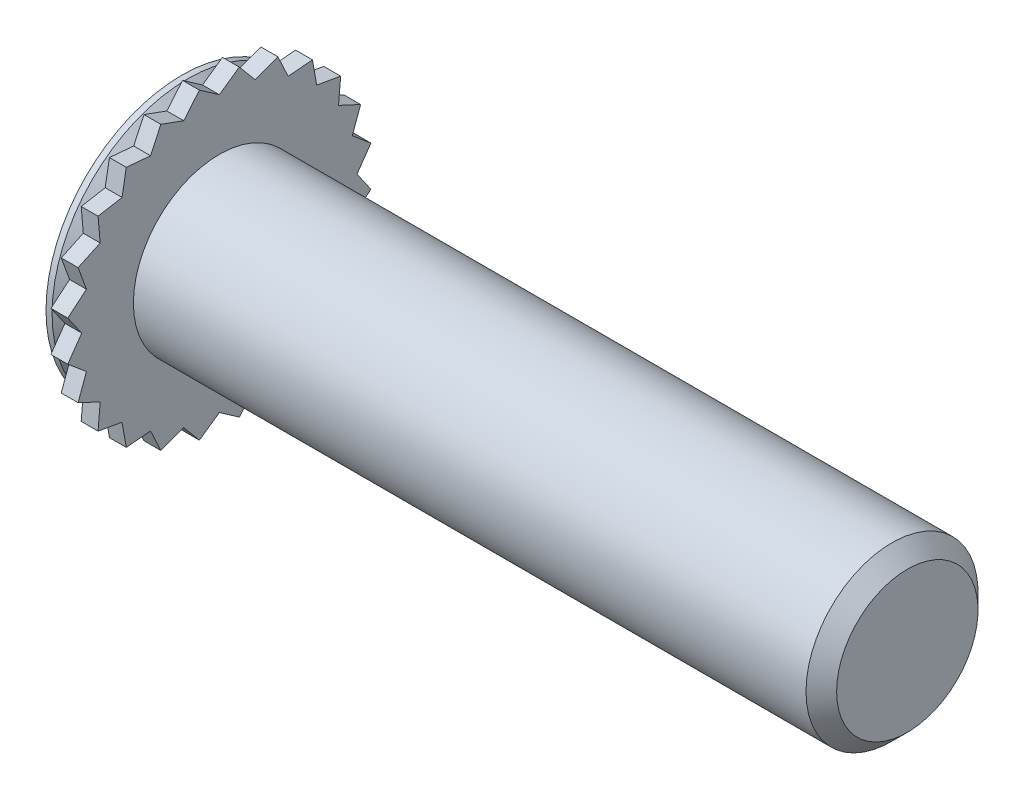
SolidWorks part; units mm, degrees
revolve "BaseBody" add sketch "BodySke" angle 360 about L6 other way angle 15
sketch "BodySke" plane through (0, 0, 0) normal (0, 0, 1) x (1, 0, 0)
  line L0 (0, 2.2225) -> (0, 3.95)
  line L1 (1.09, 4.445) -> (0.5995, 4.445)
  line L2 (0.5995, 4.445) -> (0.5995, 3.6373)
  line L3 (1.09, 2.5) -> (20.645, 2.5)
  line L4 (21.09, 2.055) -> (21.09, 0)
  line L5 (21.09, 0) -> (0.545, 0)
  line L6 (0, 0) -> (50.554, 0) construction
  line L7 (1.09, 4.445) -> (1.09, 2.5)
  line L8 (21.09, 2.055) -> (20.645, 2.5)
  line L9 (0.5995, 3.6373) -> (0.4905, 3.6373)
  line L10 (0.4905, 3.6373) -> (0.1778, 3.95)
  line L11 (1.89, 19.05) -> (1.89, -3.175) construction
  line L12 (0.1778, 3.95) -> (0, 3.95)
  line L13 (0, 2.2225) -> (0.545, 1.6775)
  line L14 (0.545, 1.6775) -> (0.545, 0)
  dimension "Advance" = 0.8
  dimension "Minor_dia" = 4.11
  dimension "Diameter" = 5
  dimension "Length" = 20
  dimension "D1" = 45
cosmetic thread "ThreadCosmetic" [suppressed] parameters "Thread_length"=18.4, "Thread_minor"=4.11
ref_plane "Plane1" through (0, 0, 0) normal (0, 0, 1) x (1, 0, 0)
ref_plane "Plane2" through (0, 0, 0) normal (0, 1, 0) x (1, 0, 0)
ref_plane "Plane3" through (0, 0, 0) normal (1, 0, 0) x (0, 0, -1)
sketch "ThdSchSke" plane through (0, 0, 0) normal (0, 0, 1) x (1, 0, 0)
  line L0 (2.69, -2.055) -> (2.3784, -2.5)
  line L1 (2.69, -2.055) -> (3.0016, -2.5)
  line L2 (3.0016, -2.5) -> (3.0016, -3.125)
  line L3 (-3.175, 0) -> (5.1513, 0) construction
  line L5 (3.0016, -3.125) -> (2.3784, -3.125)
  line L6 (2.3784, -3.125) -> (2.3784, -2.5)
  line L8 (1.09, -2.5) -> (1.09, 2.5) construction
  dimension "Diameter" = 5
  dimension "Thread_minor" = 4.11
  dimension "Start" = 1.6
revolve "ThreadSchematic" [suppressed] cut sketch "ThdSchSke" angle 360 about L3
pattern_linear "ThdSchPat" [suppressed]
sketch "CliRinCutSke" plane through (1.09, 0, 0) normal (1, 0, 0) x (0, 0, -1)
  line L0 (0, 0) -> (0, 4.8256) construction
  line L1 (0.5802, 4.407) -> (0, 4.0005)
  line L2 (0, 4.0005) -> (-0.5802, 4.407)
  arc A0 (0.5802, 4.407) -> (-0.5802, 4.407) centre (0, 0) ccw
  circle A1 centre (0, 0) radius 4.445 construction
  circle A2 centre (0, 0) radius 4.0005 construction
extrude "ClinchCut" cut sketch "CliRinCutSke" against normal blind 0.4905
pattern_circular "ClinchCutPat" count 24 every 15 about axis through (0, 0, 0) along (1, 0, 0) of "ClinchCut"
equation "' \"Length@BodySke\" = 20"
equation "' \"A_dim@BodySke\" = 1.09"
equation "' \"E_dia@BodySke\" = 8.89"
equation "' \"C_dia@BodySke\" = 7.9"
equation "' \"Diameter@BodySke\" = 5"
equation "' \"Minor_dia@BodySke\" = 4.11"
equation "' \"Advance@BodySke\" = 0.8"
equation "\"Face_clr_dia@BodySke\" = \"E_dia@BodySke\" / 2"
equation "\"Face_clr_dep@BodySke\" = \"A_dim@BodySke\" / 2"
equation "\"Start@ThdSchSke\" = 1.6"
equation "\"Skirt_ht@BodySke\" = \"A_dim@BodySke\" * 0.45"
equation "\"Clinch_ht@BodySke\" = \"A_dim@BodySke\" * 0.45"
equation "\"Depth@ClinchCut\" = \"A_dim@BodySke\" * 0.45"
equation "\"Count@ClinchCutPat\" = 24"
equation "\"Angle@ClinchCutPat\" = 360 / \"Count@ClinchCutPat\""
equation "\"Angle@CliRinCutSke\" = 360 / \"Count@ClinchCutPat\""
equation "\"Clinch_minor@CliRinCutSke\" =  \"C_dia@BodySke\" "
equation "\"Clinch_minor@CliRinCutSke\" =  \"E_dia@BodySke\" * 0.9"
equation "\"Thread_length@ThreadCosmetic\" = \"Length@BodySke\" - \"Start@ThdSchSke\""
equation "\"Thread_minor@ThreadCosmetic\" = \"Minor_dia@BodySke\""
equation "\"Thread_minor@ThdSchSke\" = \"Minor_dia@BodySke\""
equation "\"Diameter@ThdSchSke\" = \"Diameter@BodySke\""
equation "\"Overcut@ThdSchSke\" = \"Diameter@BodySke\" * 1.25"
equation "\"Num_threads@ThdSchPat\" = int( \"Thread_length@ThreadCosmetic\" / \"Advance@BodySke\" + 0.999 )  + 1"
equation "\"Advance@ThdSchPat\" = \"Thread_length@ThreadCosmetic\" /  (\"Num_threads@ThdSchPat\" - 1) 'relax it"
equation "\"Num_threads@ThdSchPat\" = \"Num_threads@ThdSchPat\" - sgn( \"Num_threads@ThdSchPat\" - 1) '---chamfered tips only---"
